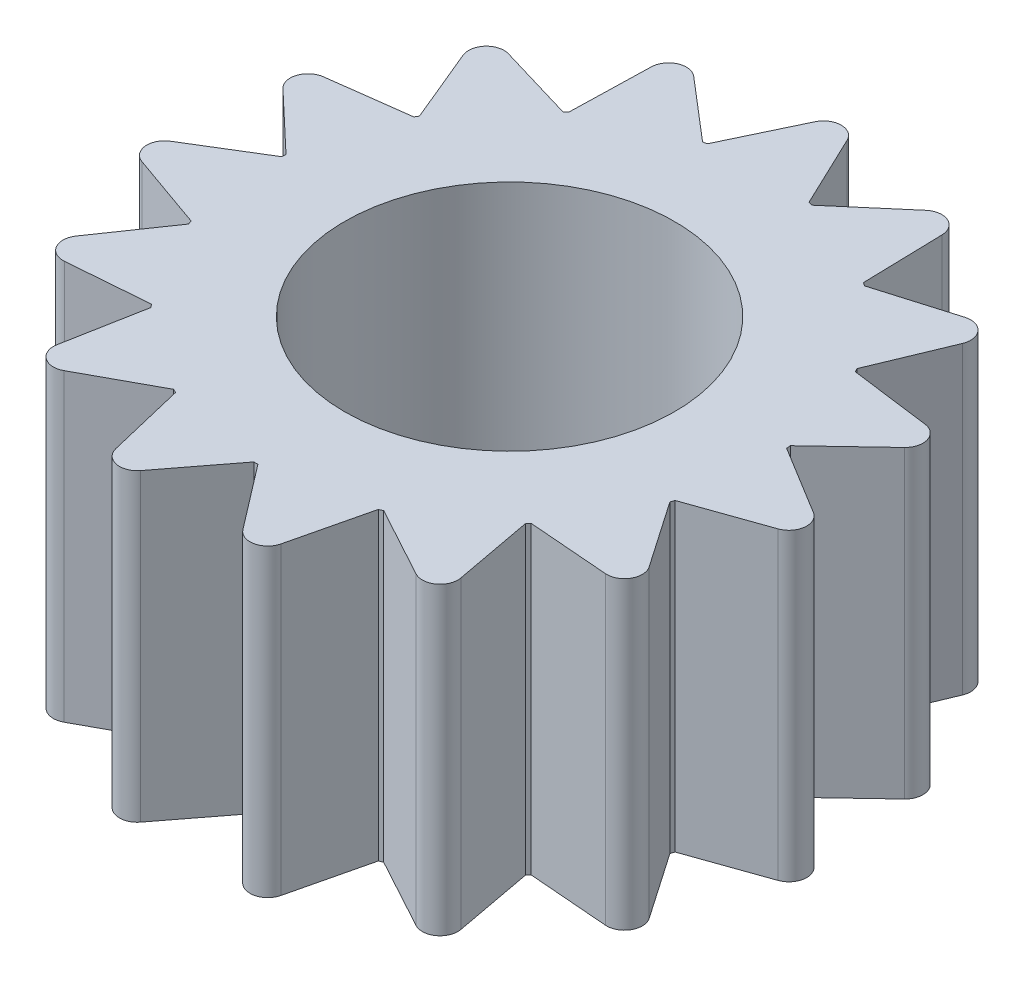
SolidWorks part; units mm, degrees
ref_plane "Front Plane" through (0, 0, 0) normal (0, 0, 1) x (1, 0, 0)
ref_plane "Top Plane" through (0, 0, 0) normal (0, 1, 0) x (1, 0, 0)
ref_plane "Right Plane" through (0, 0, 0) normal (1, 0, 0) x (0, 0, -1)
sketch "Sketch1" plane through (0, 0, 0) normal (0, 1, 0) x (1, 0, 0)
  line L0 (0, 5) -> (0, 7) construction
  line L1 (0, 7) -> (1, 4.899)
  line L2 (0, 7) -> (-1, 4.899)
  line L3 (2.8472, 6.3948) -> (1.079, 4.8822)
  line L4 (2.8472, 6.3948) -> (2.9061, 4.0687)
  line L5 (5.202, 4.6839) -> (2.9715, 4.0212)
  line L6 (5.202, 4.6839) -> (4.3098, 2.5349)
  line L7 (6.6574, 2.1631) -> (4.3502, 2.4649)
  line L8 (6.6574, 2.1631) -> (4.9682, 0.5628)
  line L9 (6.9617, -0.7317) -> (4.9767, 0.4824)
  line L10 (6.9617, -0.7317) -> (4.7676, -1.5066)
  line L11 (6.0622, -3.5) -> (4.7426, -1.5835)
  line L12 (6.0622, -3.5) -> (3.7426, -3.3155)
  line L13 (4.1145, -5.6631) -> (3.6886, -3.3756)
  line L14 (4.1145, -5.6631) -> (2.0705, -4.5511)
  line L15 (1.4554, -6.847) -> (1.9967, -4.584)
  line L16 (1.4554, -6.847) -> (0.0404, -4.9998)
  line L17 (-1.4554, -6.847) -> (-0.0404, -4.9998)
  line L18 (-1.4554, -6.847) -> (-1.9967, -4.584)
  line L19 (-4.1145, -5.6631) -> (-2.0705, -4.5511)
  line L20 (-4.1145, -5.6631) -> (-3.6886, -3.3756)
  line L21 (-6.0622, -3.5) -> (-3.7426, -3.3155)
  line L22 (-6.0622, -3.5) -> (-4.7426, -1.5835)
  line L23 (-6.9617, -0.7317) -> (-4.7676, -1.5066)
  line L24 (-6.9617, -0.7317) -> (-4.9767, 0.4824)
  line L25 (-6.6574, 2.1631) -> (-4.9682, 0.5628)
  line L26 (-6.6574, 2.1631) -> (-4.3502, 2.4649)
  line L27 (-5.202, 4.6839) -> (-4.3098, 2.5349)
  line L28 (-5.202, 4.6839) -> (-2.9715, 4.0212)
  line L29 (-2.8472, 6.3948) -> (-2.9061, 4.0687)
  line L30 (-2.8472, 6.3948) -> (-1.079, 4.8822)
  circle A0 centre (0, 0) radius 3.25
  circle A1 centre (0, 0) radius 5
  point P53 (0, 0)
  point P68 (0, 0)
  dimension "D1" = 6.5
  dimension "D2" = 10
  dimension "D4" = 2
  dimension "D3" = 2
extrude "Boss-Extrude2" add sketch "Sketch1" along normal blind 6 contours A1 | A1 | A1 | A1 A0 | A1 | A1 | A1 | A1 L0 L2 | L0 A1 L1 | A1 | A1 | A1 | A1 | A1 | A1 | A1 | A1 | A1 | A1 | A1 | A1 | A1 region at (-0.3304, 0, -5.6446) region at (0.3304, 0, -5.6446) region at (0.4883, 0, -4.834) region at (2.2959, 0, -5.1566) region at (-2.2959, 0, -5.1566) region at (4.1948, 0, -3.777) region at (-4.1948, 0, -3.777) region at (5.3684, 0, -1.7443) region at (-5.3684, 0, -1.7443) region at (5.6137, 0, 0.59) region at (-5.6137, 0, 0.59) region at (-4.8884, 0, 2.8223) region at (4.8884, 0, 2.8223) region at (-3.3178, 0, 4.5666) region at (3.3178, 0, 4.5666) region at (-1.1736, 0, 5.5213) region at (1.1736, 0, 5.5213)
fillet "Fillet1" radius 0.35 15 edges at (0, 3, -7) (2.8472, 3, -6.3948) (5.202, 3, -4.6839) (6.6574, 3, -2.1631) (6.9617, 3, 0.7317) (6.0622, 3, 3.5) (4.1145, 3, 5.6631) (1.4554, 3, 6.847) (-1.4554, 3, 6.847) (-4.1145, 3, 5.6631) (-6.0622, 3, 3.5) (-6.9617, 3, 0.7317) (-2.8472, 3, -6.3948) (-5.202, 3, -4.6839) (-6.6574, 3, -2.1631)
